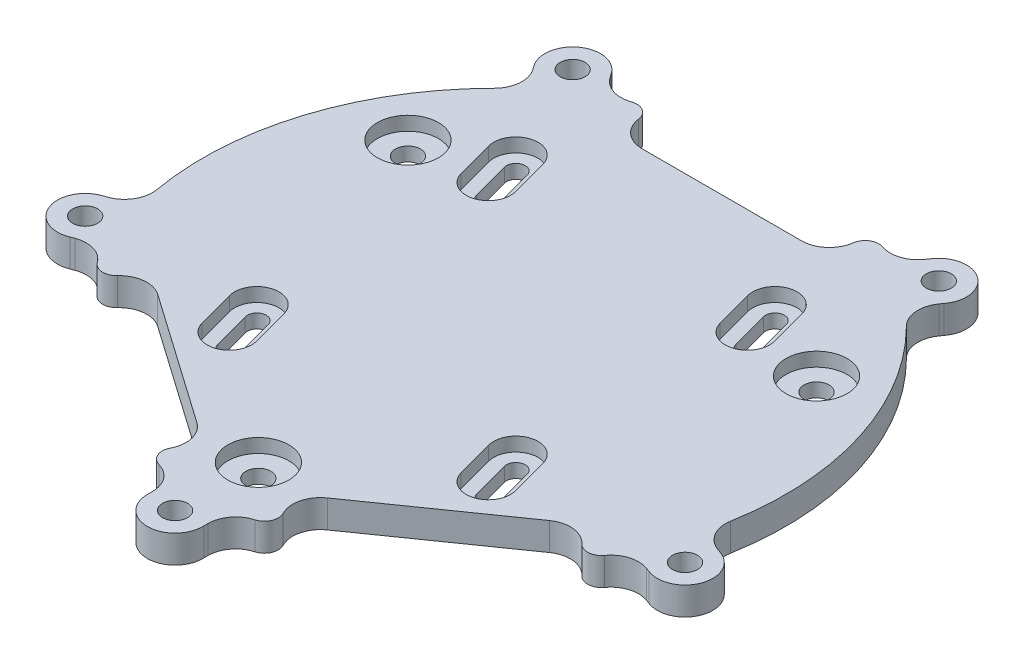
SolidWorks part; units mm, degrees
ref_plane "Plan de face" through (0, 0, 0) normal (0, 0, 1) x (1, 0, 0)
ref_plane "Plan de dessus" through (0, 0, 0) normal (0, 1, 0) x (1, 0, 0)
ref_plane "Plan de droite" through (0, 0, 0) normal (1, 0, 0) x (0, 0, -1)
sketch "Sketch1" plane through (0, 0, 0) normal (0, 1, 0) x (1, 0, 0)
  line L0 (0, 0) -> (0, 41) construction
  line L1 (0, 0) -> (-23.5166, -33.5852) construction
  line L2 (0, 0) -> (23.5166, -33.5852) construction
  line L3 (-39.3263, -22.5152) -> (-7.707, -44.6553)
  line L4 (7.707, -44.6553) -> (39.3263, -22.5152)
  line L5 (-19.3, 41) -> (19.3, 41)
  line L6 (-19.3, 41) -> (-19.3, 48.8238)
  line L8 (19.3, 41) -> (19.3, 48.8238)
  line L9 (7.707, -44.6553) -> (12.1945, -51.0641)
  line L11 (39.3263, -22.5152) -> (43.8138, -28.9241)
  line L12 (-7.707, -44.6553) -> (-12.1945, -51.0641)
  line L13 (-39.3263, -22.5152) -> (-43.8138, -28.9241)
  line L14 (0, 0) -> (0, -42.5) construction
  line L15 (0, 0) -> (-36.8061, 21.25) construction
  line L16 (0, 0) -> (36.8061, 21.25) construction
  arc A0 (-19.3, 48.8238) -> (-43.8138, -28.9241) centre (0, 0) ccw
  arc A1 (43.8138, -28.9241) -> (19.3, 48.8238) centre (0, 0) ccw
  circle A3 centre (-36.8061, 21.25) radius 2.25 construction
  circle A4 centre (36.8061, 21.25) radius 2.25 construction
  circle A6 centre (0, -42.5) radius 2.25 construction
  arc A7 (-12.1945, -51.0641) -> (12.1945, -51.0641) centre (0, 0) ccw
  circle A8 centre (-36.8061, 21.25) radius 5.5
  circle A9 centre (36.8061, 21.25) radius 5.5
  circle A10 centre (0, -42.5) radius 5.5
  point P25 (23.5166, -33.5852)
  point P26 (-23.5166, -33.5852)
  dimension "D1" = 105
  dimension "D5" = 35
  dimension "D6" = 38.6
  dimension "D10" = 4.5
  dimension "D4" = 11
  dimension "D9" = 42.5
  dimension "D2" = 35
  dimension "D3" = 41
  dimension "D7" = 120
  dimension "D8" = 120
extrude "Boss-Extrude1" add sketch "Sketch1" along normal blind 5 contours L4 A0 L5 L3 | A8 | A9 | A10 region at (0, 0, -1.6314) region at (-36.8061, 0, -21.25) region at (36.8061, 0, -21.25) region at (0, 0, 42.5)
sketch "Esquisse1" plane through (0, 5, 0) normal (0, 1, 0) x (1, 0, 0)
  line L0 (0, 0) -> (-23.3345, 23.3345) construction
  line L1 (0, 0) -> (0, 41) construction
  line L2 (-19.3, 41) -> (19.3, 41) construction
  line L3 (-24.758, 28.6471) -> (-22.9463, 21.8856) construction
  line L4 (-23.116, 29.0871) -> (-21.3042, 22.3256)
  line L5 (-26.4001, 28.2071) -> (-24.5884, 21.4456)
  line L6 (0, 0) -> (23.3345, 23.3345) construction
  line L7 (0, 0) -> (23.3345, -23.3345) construction
  line L8 (0, 0) -> (-23.3345, -23.3345) construction
  line L9 (23.7228, 21.8856) -> (21.911, 28.6471) construction
  line L10 (22.0807, 21.4456) -> (20.2689, 28.2071)
  line L11 (25.3648, 22.3256) -> (23.5531, 29.0871)
  line L12 (23.7228, -24.7834) -> (21.911, -18.0219) construction
  line L13 (22.0807, -25.2234) -> (20.2689, -18.4619)
  line L14 (25.3648, -24.3434) -> (23.5531, -17.5819)
  line L15 (-22.9463, -24.7834) -> (-24.758, -18.0219) construction
  line L16 (-24.5884, -25.2234) -> (-26.4001, -18.4619)
  line L17 (-21.3042, -24.3434) -> (-23.116, -17.5819)
  line L18 (0, 0) -> (-10.9859, 41) construction
  line L19 (-22.9463, 21.8856) -> (-24.758, 28.6471) construction
  line L20 (-26.81, 20.8504) -> (-28.6217, 27.6118)
  line L21 (-19.0826, 22.9209) -> (-20.8943, 29.6824)
  line L22 (23.7228, 21.8856) -> (21.911, 28.6471) construction
  line L23 (19.859, 20.8504) -> (18.0473, 27.6118)
  line L24 (27.5865, 22.9209) -> (25.7747, 29.6824)
  line L25 (23.7228, -24.7834) -> (21.911, -18.0219) construction
  line L26 (19.859, -25.8187) -> (18.0473, -19.0572)
  line L27 (27.5865, -23.7481) -> (25.7747, -16.9867)
  line L28 (-22.9463, -24.7834) -> (-24.758, -18.0219) construction
  line L29 (-26.81, -25.8187) -> (-28.6217, -19.0572)
  line L30 (-19.0826, -23.7481) -> (-20.8943, -16.9867)
  arc A0 (-23.116, 29.0871) -> (-26.4001, 28.2071) centre (-24.758, 28.6471) ccw
  arc A1 (-24.5884, 21.4456) -> (-21.3042, 22.3256) centre (-22.9463, 21.8856) ccw
  arc A2 (22.0807, 21.4456) -> (25.3648, 22.3256) centre (23.7228, 21.8856) ccw
  arc A3 (23.5531, 29.0871) -> (20.2689, 28.2071) centre (21.911, 28.6471) ccw
  arc A4 (22.0807, -25.2234) -> (25.3648, -24.3434) centre (23.7228, -24.7834) ccw
  arc A5 (23.5531, -17.5819) -> (20.2689, -18.4619) centre (21.911, -18.0219) ccw
  arc A6 (-24.5884, -25.2234) -> (-21.3042, -24.3434) centre (-22.9463, -24.7834) ccw
  arc A7 (-23.116, -17.5819) -> (-26.4001, -18.4619) centre (-24.758, -18.0219) ccw
  arc A8 (-26.81, 20.8504) -> (-19.0826, 22.9209) centre (-22.9463, 21.8856) ccw
  arc A9 (-20.8943, 29.6824) -> (-28.6217, 27.6118) centre (-24.758, 28.6471) ccw
  arc A10 (19.859, 20.8504) -> (27.5865, 22.9209) centre (23.7228, 21.8856) ccw
  arc A11 (25.7747, 29.6824) -> (18.0473, 27.6118) centre (21.911, 28.6471) ccw
  arc A12 (19.859, -25.8187) -> (27.5865, -23.7481) centre (23.7228, -24.7834) ccw
  arc A13 (25.7747, -16.9867) -> (18.0473, -19.0572) centre (21.911, -18.0219) ccw
  arc A14 (-26.81, -25.8187) -> (-19.0826, -23.7481) centre (-22.9463, -24.7834) ccw
  arc A15 (-20.8943, -16.9867) -> (-28.6217, -19.0572) centre (-24.758, -18.0219) ccw
  point P8 (-23.8522, 25.2664)
  point P18 (22.8169, 25.2664)
  point P25 (22.8169, -21.4027)
  point P30 (-23.8522, -21.4027)
  point P40 (-23.8522, 25.2664)
  point P45 (22.8169, 25.2664)
  point P52 (22.8169, -21.4027)
  point P59 (-23.8522, -21.4027)
  dimension "D5" = 1.7
  dimension "D9" = 4
  dimension "D1" = 1.5
  dimension "D2" = 5.5
  dimension "D3" = 15
  dimension "D4" = 33
  dimension "D6" = 45
  dimension "D7" = 1.5
  dimension "D8" = 30
extrude "Enlèv. mat.-Extru.1" cut sketch "Esquisse1" against normal up to next contours L5 A1 L4 A0 | L11 A3 L10 A2 | L14 A5 L13 A4 | L17 A7 L16 A6 region at (-23.8522, 5, -25.2664) region at (22.8169, 5, -25.2664) region at (22.8169, 5, 21.4027) region at (-23.8522, 5, 21.4027)
extrude "Enlèv. mat.-Extru.2" cut sketch "Esquisse1<3>" against normal blind 2.5
sketch "Esquisse1<3>" plane through (0, 5, 0) normal (0, 1, 0) x (1, 0, 0) same geometry as "Esquisse1"
extrude "Enlèv. mat.-Extru.3" cut sketch "Sketch1<3>" against normal blind 2.5 from surface contours A8 | A9 | A10 region at (-36.8061, 0, -21.25) region at (36.8061, 0, -21.25) region at (0, 0, 42.5) starting at face at (-23.8522, 5, 21.4027)
sketch "Sketch1<3>" plane through (0, 0, 0) normal (0, 1, 0) x (1, 0, 0) same geometry as "Sketch1"
hole_wizard "M4 Clearance Hole1" positions "Esquisse4" profile "Esquisse3" hole size "M4" standard "ANSI Metric" end condition up to next
sketch "Esquisse4" plane through (0, 5, 0) normal (0, 1, 0) x (1, 0, 0)
  point P0 (0, -42.5)
  point P3 (36.8061, 21.25)
  point P6 (-36.8061, 21.25)
sketch "Esquisse3" plane through (0, 5, 42.5) normal (1, 0, 0) x (0, 0, 1)
  line L0 (0, 0) -> (0, 5)
  line L1 (0, 5) -> (2.25, 5)
  line L2 (2.25, 5) -> (2.25, 0)
  line L5 (2.25, 0) -> (0, 0)
  line L11 (0, -6.35) -> (0, 107.95) construction
  dimension "Thru Hole Dia." = 4.5
  dimension "Thru Hole Depth" = 5
fillet "Congé1" radius 2.5 6 edges at (19.3, 2.5, -48.8238) (-19.3, 2.5, -48.8238) (-43.8138, 2.5, 28.9241) (43.8138, 2.5, 28.9241) (12.1945, 2.5, 51.0641) (-12.1945, 2.5, 51.0641)
sketch "Esquisse5" plane through (0, 5, 0) normal (0, 1, 0) x (1, 0, 0)
  line L0 (0, 0) -> (0, -57.5) construction
  line L1 (0, 0) -> (54.0323, -19.6662) construction
  line L2 (0, 0) -> (32.9806, 47.1012) construction
  line L3 (0, 0) -> (-32.9806, 47.1012) construction
  line L4 (0, 0) -> (-54.0323, -19.6662) construction
  line L5 (-52.1196, -24.2858) -> (-47.4016, -22.5686)
  line L6 (-55.5365, -14.8978) -> (-50.8185, -13.1806)
  line L7 (-36.9478, 44.058) -> (-34.068, 39.9452)
  line L8 (-28.7641, 49.7883) -> (-25.8843, 45.6755)
  line L9 (36.9478, 44.058) -> (34.068, 39.9452)
  line L10 (28.7641, 49.7883) -> (25.8843, 45.6755)
  line L11 (52.1196, -24.2858) -> (47.4016, -22.5686)
  line L12 (55.5365, -14.8978) -> (50.8185, -13.1806)
  line L13 (4.9953, -57.2826) -> (4.9953, -52.2618)
  line L14 (-4.9953, -57.2826) -> (-4.9953, -52.2618)
  arc A0 (-4.9953, -57.2826) -> (-52.1196, -24.2858) centre (0, 0) ccw construction
  arc A1 (52.1196, -24.2858) -> (55.5365, -14.8978) centre (54.0323, -19.6662) ccw
  arc A2 (-4.9953, -57.2826) -> (4.9953, -57.2826) centre (0, -57.5) ccw
  arc A3 (-55.5365, -14.8978) -> (-52.1196, -24.2858) centre (-54.0323, -19.6662) ccw
  arc A4 (-28.7641, 49.7883) -> (-36.9478, 44.058) centre (-32.9806, 47.1012) ccw
  arc A5 (36.9478, 44.058) -> (28.7641, 49.7883) centre (32.9806, 47.1012) ccw
  arc A6 (-8.3495, -51.8318) -> (8.3495, -51.8318) centre (0, 0) ccw construction
  arc A7 (-22.89, 47.2472) -> (-45.8503, -25.5735) centre (0, 0) ccw construction
  arc A8 (45.8503, -25.5735) -> (22.89, 47.2472) centre (0, 0) ccw construction
  arc A9 (-8.3495, -51.8318) -> (8.3495, -51.8318) centre (0, 0) ccw construction
  arc A10 (47.4016, -22.5686) -> (50.8185, -13.1806) centre (0, 0) ccw
  arc A11 (34.068, 39.9452) -> (25.8843, 45.6755) centre (0, 0) ccw
  arc A12 (-25.8843, 45.6755) -> (-34.068, 39.9452) centre (0, 0) ccw
  arc A13 (-50.8185, -13.1806) -> (-47.4016, -22.5686) centre (0, 0) ccw
  arc A14 (-4.9953, -52.2618) -> (4.9953, -52.2618) centre (0, 0) ccw
  dimension "D1" = 70
  dimension "D5" = 10
  dimension "D2" = 70
  dimension "D3" = 75
  dimension "D4" = 75
extrude "Boss.-Extru.1" add sketch "Esquisse5" against normal up to surface (5 mm away) up to face at (0, 0, 44.75)
hole_wizard "M4 Clearance Hole2" positions "Esquisse8" profile "Esquisse7" hole size "M4" standard "ANSI Metric" end condition up to next
sketch "Esquisse8" plane through (0, 5, 0) normal (0, 1, 0) x (1, 0, 0)
  point P0 (0, -57.5)
  point P3 (54.0323, -19.6662)
  point P6 (32.9806, 47.1012)
  point P9 (-32.9806, 47.1012)
  point P12 (-54.0323, -19.6662)
sketch "Esquisse7" plane through (0, 5, 57.5) normal (1, 0, 0) x (0, 0, 1)
  line L0 (0, 0) -> (0, 5)
  line L1 (0, 5) -> (2.25, 5)
  line L2 (2.25, 5) -> (2.25, 0)
  line L5 (2.25, 0) -> (0, 0)
  line L11 (0, -6.35) -> (0, 107.95) construction
  dimension "Thru Hole Dia." = 4.5
  dimension "Thru Hole Depth" = 5
fillet "Congé2" radius 5 16 edges at (47.4016, 2.5, 22.5686) (50.8185, 2.5, 13.1806) (34.068, 2.5, -39.9452) (-34.068, 2.5, -39.9452) (-50.8185, 2.5, 13.1806) (-47.4016, 2.5, 22.5686) (4.9953, 2.5, 52.2618) (-4.9953, 2.5, 52.2618) (25.8843, 2.5, -45.6755) (-25.8843, 2.5, -45.6755) (-7.707, 2.5, 44.6553) (-39.3263, 2.5, 22.5152) (-19.3, 2.5, -41) (19.3, 2.5, -41) (39.3263, 2.5, 22.5152) (7.707, 2.5, 44.6553)
